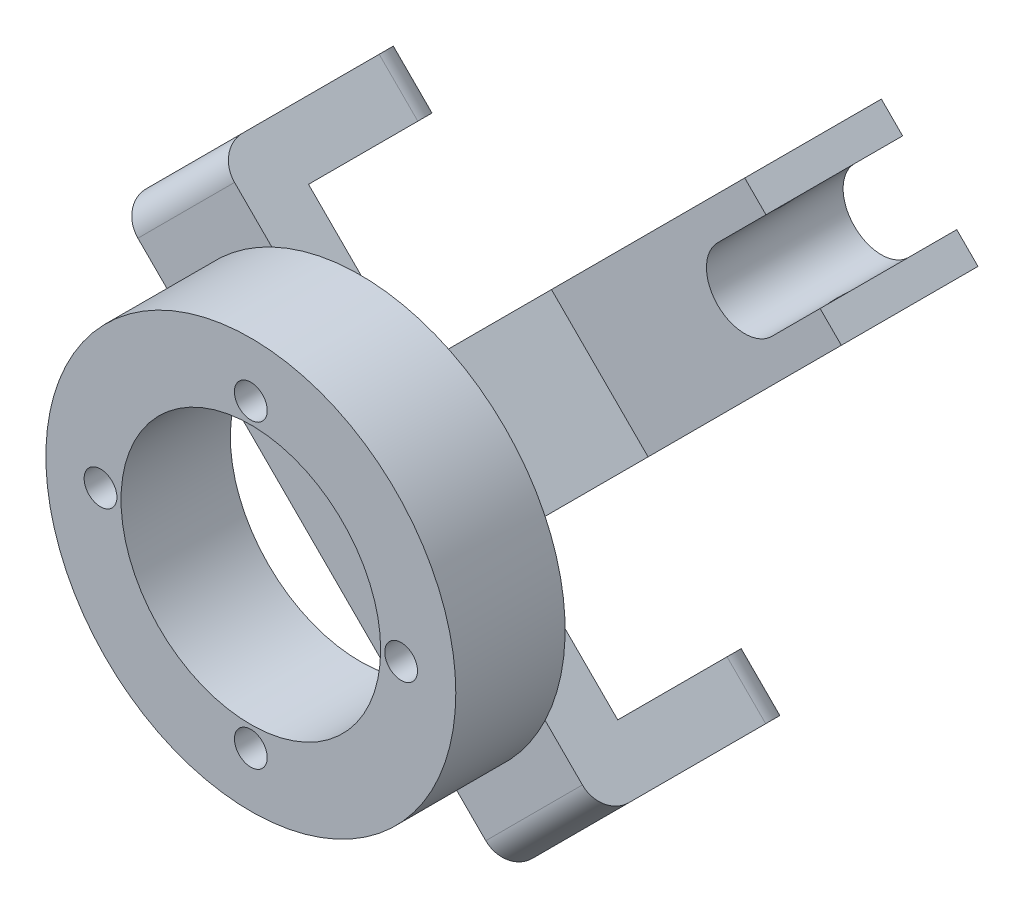
SolidWorks part; units mm, degrees
ref_plane "Płaszczyzna przednia" through (0, 0, 0) normal (0, 0, 1) x (1, 0, 0)
ref_plane "Płaszczyzna górna" through (0, 0, 0) normal (0, 1, 0) x (1, 0, 0)
ref_plane "Płaszczyzna prawa" through (0, 0, 0) normal (1, 0, 0) x (0, 0, -1)
sketch "Szkic1" plane through (0, 0, 0) normal (0, 0, 1) x (1, 0, 0)
  circle A0 centre (0, 0) radius 75
  dimension "D1" = 150
extrude "Dodanie-wyciągnięcie1" add sketch "Szkic1" along normal blind 40
sketch "Szkic2" plane through (0, 0, 40) normal (0, 0, 1) x (1, 0, 0)
  circle A0 centre (-55, 0) radius 6
  circle A1 centre (0, 55) radius 6
  circle A2 centre (55, 0) radius 6
  circle A3 centre (0, -55) radius 6
  point P12 (0, 0)
  dimension "D1" = 12
  dimension "D2" = 55
  dimension "D3" = 4
extrude "Wytnij-wyciągnięcie1" cut sketch "Szkic2" against normal blind 40
sketch "Szkic3" plane through (0, 0, 40) normal (0, 0, 1) x (1, 0, 0)
  circle A0 centre (0, 0) radius 47.5
  dimension "D1" = 95
extrude "Wytnij-wyciągnięcie2" cut sketch "Szkic3" against normal blind 40
ref_plane "Płaszczyzna1" through (0, 0, 0) normal (0.7071, -0.7071, 0) x (-0.7071, -0.7071, 0)
sketch "Szkic4" plane through (0, 0, 0) normal (0.7071, -0.7071, 0) x (-0.7071, -0.7071, 0)
  line L0 (75, 0) -> (-75, 0) construction
  line L1 (-25, 0) -> (25, 0)
  line L2 (-25, 0) -> (-25, 20)
  line L3 (-25, 20) -> (25, 20)
  line L4 (25, 0) -> (25, 20)
  dimension "D1" = 25
  dimension "D2" = 50
  dimension "D3" = 20
extrude "Dodanie-wyciągnięcie2" add sketch "Szkic4" along normal mid plane 200
sketch "Szkic6" plane through (70.7107, -70.7107, 0) normal (0.7071, -0.7071, 0) x (0, 0, -1)
  line L1 (20, 25) -> (70, 25)
  line L2 (20, 25) -> (20, -24.9998)
  line L3 (20, -24.9998) -> (70, -24.9998)
  line L4 (70, 25) -> (70, -24.9998)
  dimension "D1" = 50
extrude "Dodanie-wyciągnięcie3" add sketch "Szkic6" against normal blind 20
mirror "Lustro1" about plane through (0, 0, 0) normal (0.7071, -0.7071, 0) of "Dodanie-wyciągnięcie3"
sketch "Szkic7" plane through (-70.7107, 70.7107, 0) normal (-0.7071, 0.7071, 0) x (0, 0, 1)
  line L0 (-70, -24.9998) -> (-70, 25) construction
  circle A0 centre (-45, 0) radius 7
  dimension "D1" = 14
  dimension "D2" = 25
extrude "Wytnij-wyciągnięcie3" cut sketch "Szkic7" against normal through all
fillet "Zaokrąglenie1" radius 10 4 edges at (45.9621, -81.3171, -70) (81.3173, -45.9619, -70) (-45.9619, 81.3173, -70) (-81.3171, 45.9621, -70)
fillet "Zaokrąglenie2" radius 10 2 edges at (70.7107, -70.7107, 0) (-70.7107, 70.7107, 0)
sketch "Szkic8" plane through (0, 0, -20) normal (0, 0, -1) x (-1, 0, 0)
  line L0 (0, 35.3553) -> (35.3553, 0)
  line L1 (0, 60.5) -> (0, -60.5) construction
  line L2 (60.5, 0) -> (-60.5, 0) construction
  line L3 (35.3553, 0) -> (0, -35.3553)
  line L4 (-53.033, -88.3883) -> (88.3883, 53.033) construction
  line L5 (0, -35.3553) -> (-35.3553, 0)
  line L6 (-35.3553, 0) -> (0, 35.3553)
  dimension "D1" = 50
  dimension "D2" = 50
extrude "Dodanie-wyciągnięcie4" add sketch "Szkic8" along normal blind 100
sketch "Szkic10" plane through (17.6777, 17.6777, 0) normal (0.7071, 0.7071, 0) x (0, 0, -1)
  line L0 (120, -25) -> (20, -25) construction
  line L1 (120, 25) -> (70, 25)
  line L2 (120, 25) -> (120, -25)
  line L3 (120, -25) -> (70, -25)
  line L4 (70, 25) -> (70, -25)
  dimension "D1" = 50
extrude "Dodanie-wyciągnięcie5" add sketch "Szkic10" along normal blind 100
sketch "Szkic12" plane through (17.6777, -17.6777, 0) normal (0.7071, -0.7071, 0) x (0, 0, -1)
  line L1 (70, 125) -> (70, 25) construction
  line L4 (70, 125) -> (120, 125) construction
  circle A0 centre (95, 105) radius 7
  dimension "D3" = 14
  dimension "D1" = 25
  dimension "D2" = 20
extrude "Wytnij-wyciągnięcie5" cut sketch "Szkic12" against normal through all
sketch "Szkic14" plane through (0, 0, -120) normal (0, 0, -1) x (-1, 0, 0)
  line L0 (-38.8909, 38.8909) -> (38.8909, -38.8909) construction
  line L1 (-106.066, 70.7107) -> (-70.7107, 106.066) construction
  line L3 (35.3553, 0) -> (-70.7107, 106.066) construction
  line L7 (-80.6102, 60.8112) -> (-98.2878, 78.4889)
  line L10 (-60.8112, 80.6102) -> (-78.4889, 98.2878)
  line L11 (-78.4889, 98.2878) -> (-98.2878, 78.4889)
  arc A0 (-80.6102, 60.8112) -> (-60.8112, 80.6102) centre (-70.7107, 70.7107) ccw
  dimension "D1" = 28
  dimension "D2" = 25
  dimension "D3" = 25
extrude "Wytnij-wyciągnięcie6" cut sketch "Szkic14" against normal through all
